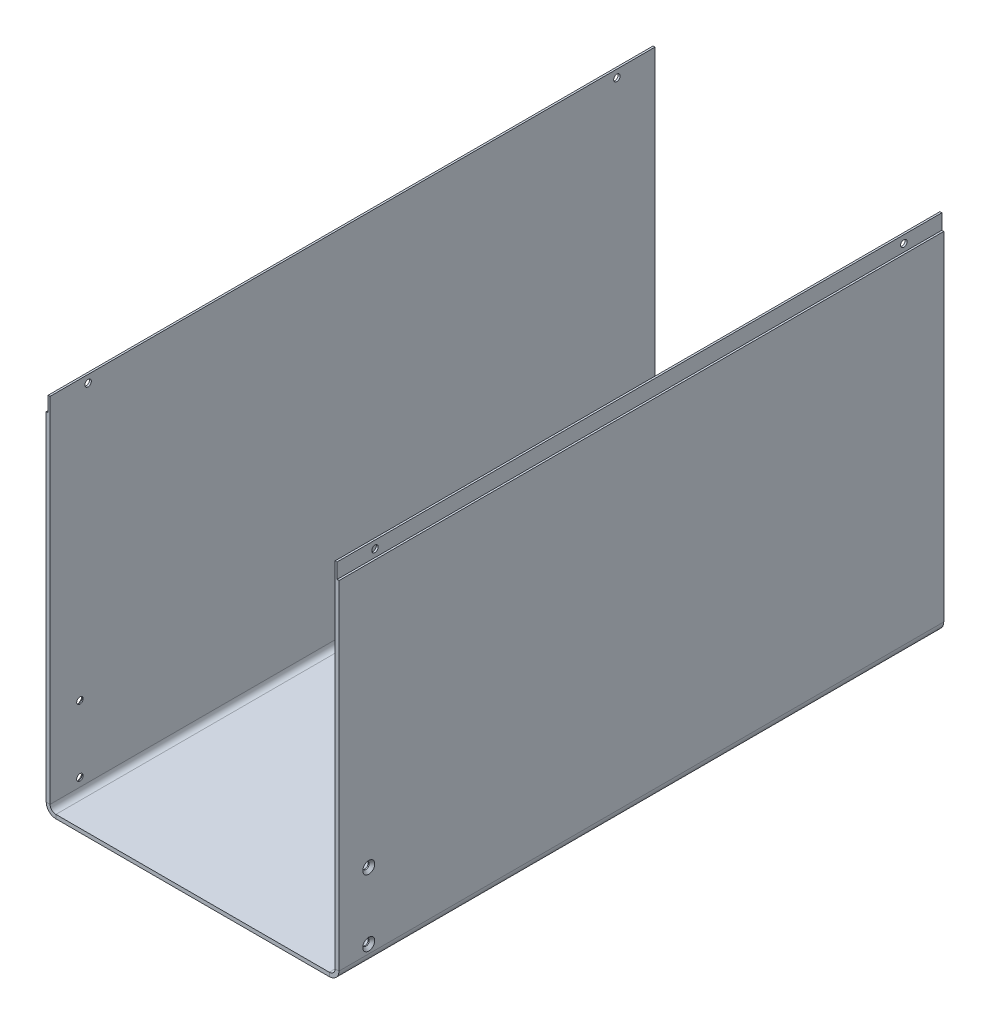
SolidWorks part; units mm, degrees
note: The reader was unsure of these and kept them because the rebuilt part matched: flange length of "Edge-Flange1"; thickness of "Edge-Flange1".
ref_plane "Front Plane" through (0, 0, 0) normal (0, 0, 1) x (1, 0, 0)
ref_plane "Top Plane" through (0, 0, 0) normal (0, 1, 0) x (1, 0, 0)
ref_plane "Right Plane" through (0, 0, 0) normal (1, 0, 0) x (0, 0, -1)
sketch "Sketch1" plane through (0, 0, 0) normal (0, 1, 0) x (1, 0, 0)
  line L1 (0, 0) -> (150, 0)
  line L2 (0, 0) -> (0, 318.3528)
  line L3 (0, 318.3528) -> (150, 318.3528)
  line L4 (150, 0) -> (150, 318.3528)
  line L7 (146.952, 318.3528) -> (3.048, 318.3528) construction
  line L8 (75, 318.3528) -> (75, 354.3857) construction
  line L9 (292.8203, 354.3857) -> (127.8203, 354.3857) construction
  dimension "D1" = 150
base flange "Base-Flange1" sketch "Sketch1" thickness 2.032 reverse thickness direction no parameters "D1"=3.048
edge flange "Edge-Flange1" sketch "Sketch6" flange profiles "Sketch6", "Sketch8" flange angle 90 flange length 189.048 flange position material outside bend radius 3.048 thickness 2.032 relief rectangular parameters "D6"=10, "D8"=1
sketch "Sketch6" plane through (150, 0, 0) normal (1, 0, 0) x (0, 0, -1)
  line L2 (0, 0) -> (0, 189.048)
  line L3 (0, 189.048) -> (318.3528, 189.048)
  line L4 (318.3528, 189.048) -> (318.3528, 0)
  line L7 (0, 0) -> (318.3528, 0) construction
  line L8 (0, 0) -> (318.3528, 0)
sketch "Sketch8" plane through (0, 0, 0) normal (-1, 0, 0) x (0, 0, 1)
  line L0 (-318.3528, 0) -> (0, 0) construction
  line L1 (-318.3528, 0) -> (0, 0)
  line L2 (-318.3528, 0) -> (-318.3528, 189.048)
  line L3 (-318.3528, 189.048) -> (0, 189.048)
  line L4 (0, 189.048) -> (0, 0)
bend "EdgeBend1" bend radius 3.048 bend angle 90 parameters "D5"=1
bend "EdgeBend2" bend radius 3.048 bend angle 90 parameters "D5"=3
sketch "Sketch9" plane through (152.032, 0, 0) normal (1, 0, 0) x (0, 0, -1)
  line L0 (318.3528, 3.048) -> (318.3528, 189.048) construction
  line L1 (0, 189.048) -> (318.3528, 189.048)
  line L2 (0, 189.048) -> (0, 181.048)
  line L3 (0, 181.048) -> (318.3528, 181.048)
  line L4 (318.3528, 189.048) -> (318.3528, 181.048)
  dimension "D1" = 8
extrude "Cut-Extrude1" cut sketch "Sketch9" against normal blind 1.016 normal cut yes
sketch "Sketch10" plane through (-2.032, 0, -3.175) normal (1, 0, 0) x (0, 0, -1)
  line L1 (-3.175, 189.048) -> (315.1778, 189.048)
  line L2 (-3.175, 189.048) -> (-3.175, 181.048)
  line L3 (-3.175, 181.048) -> (315.1778, 181.048)
  line L4 (315.1778, 189.048) -> (315.1778, 181.048)
  line L5 (-3.175, 3.048) -> (-3.175, 189.048) construction
  dimension "D1" = 8
extrude "Cut-Extrude3" cut sketch "Sketch10" along normal blind 1.016 normal cut yes
sketch "Sketch11" plane through (151.016, 0, 0) normal (1, 0, 0) x (0, 0, -1)
  line L0 (0, 185.048) -> (20.0033, 185.048) construction
  line L1 (0, 189.048) -> (0, 181.048) construction
  line L2 (318.3528, 185.048) -> (298.3528, 185.048) construction
  line L3 (318.3528, 181.048) -> (318.3528, 189.048) construction
  dimension "D1" = 20.0033
  dimension "D2" = 20
hole_wizard "M3 Clearance Hole1" positions "Sketch12" profile "Sketch13" hole size "M3" standard "ANSI Metric" end condition through all
sketch "Sketch12" plane through (151.016, 0, 0) normal (1, 0, 0) x (0, 0, -1)
  point P0 (20.0033, 185.048)
  point P3 (298.3528, 185.048)
sketch "Sketch13" plane through (151.016, 185.048, -20.0033) normal (0, 1, 0) x (0, 0, -1)
  line L0 (0, 0) -> (0, 153.048)
  line L1 (0, 153.048) -> (1.7, 153.048)
  line L2 (1.7, 153.048) -> (1.7, 0)
  line L5 (1.7, 0) -> (0, 0)
  line L11 (0, -6.35) -> (0, 107.95) construction
  dimension "Thru Hole Dia." = 3.4
  dimension "Thru Hole Depth" = 153.048
sketch "Sketch16" plane through (152.032, 0, 0) normal (1, 0, 0) x (0, 0, -1)
  line L0 (5.5, 181.048) -> (5.5, 175.048) construction
  line L1 (0, 181.048) -> (318.3528, 181.048) construction
  line L2 (5.5, 175.048) -> (0, 175.048) construction
  line L3 (0, 181.048) -> (0, 3.048) construction
  dimension "D1" = 6
  dimension "D2" = 5.5
hole_wizard "CSK for M3 Flat Head Machine Screw1" positions "Sketch19" profile "Sketch20" countersink size "M3" standard "ANSI Metric" end condition up to next
sketch "Sketch19" plane through (152.032, 0, 0) normal (1, 0, 0) x (0, 0, -1)
  point P0 (15.7004, 42.5)
  point P6 (15.7004, 7.5)
sketch "Sketch20" plane through (152.032, 42.5, -15.7004) normal (0, 1, 0) x (0, 0, -1)
  line L0 (0, 0) -> (0, 2.032)
  line L1 (0, 2.032) -> (1.7, 2.032)
  line L2 (1.7, 2.032) -> (1.7, 1.45)
  line L3 (1.7, 1.45) -> (3.15, 0)
  line L5 (3.15, 0) -> (0, 0)
  line L6 (-1.7, 1.45) -> (-3.15, 0) construction
  line L11 (0, -6.35) -> (0, 107.95) construction
  dimension "Thru Hole Dia." = 3.4
  dimension "Thru Hole Depth" = 2.032
  dimension "Near C'Sink Dia." = 6.3
  dimension "Near C'Sink Angle" = 90
hole_wizard "CSK for M3 Flat Head Machine Screw2" positions "Sketch22" profile "Sketch23" countersink size "M3" standard "ANSI Metric" end condition up to next
sketch "Sketch22" plane through (-2.032, 0, 0) normal (-1, 0, 0) x (0, 0, 1)
  point P0 (-15.7004, 42.5)
  point P3 (-15.7004, 7.5)
sketch "Sketch23" plane through (-2.032, 42.5, -15.7004) normal (0, 1, 0) x (0, 0, 1)
  line L0 (0, 0) -> (0, 2.032)
  line L1 (0, 2.032) -> (1.7, 2.032)
  line L2 (1.7, 2.032) -> (1.7, 1.45)
  line L3 (1.7, 1.45) -> (3.15, 0)
  line L5 (3.15, 0) -> (0, 0)
  line L6 (-1.7, 1.45) -> (-3.15, 0) construction
  line L11 (0, -6.35) -> (0, 107.95) construction
  dimension "Thru Hole Dia." = 3.4
  dimension "Thru Hole Depth" = 2.032
  dimension "Near C'Sink Dia." = 6.3
  dimension "Near C'Sink Angle" = 90
sketch "Bend-Lines1" [suppressed] plane through (0, 0, 0) normal (0, 1, 0) x (1, 0, 0)
sketch "Bounding-Box1" [suppressed] plane through (0, 0, 0) normal (0, 1, 0) x (1, 0, 0)
sheet metal parameters "Sheet-Metal1" thickness 2.032 parameters "D1"=1.016
flat pattern "Flat-Pattern1" [suppressed]
sketch "Bend-Lines2" plane through (0, 0, 0) normal (0, 1, 0) x (1, 0, 0)
sketch3d "Bounding-Box2" [suppressed]
  line L0 (0, 0, 0) -> (0, 326.228, 0) construction
  line L1 (150, 0, 0) -> (150, 326.228, 0) construction
  line L2 (0, 0, 0) -> (150, 0, 0) construction
  line L3 (0, 326.228, 0) -> (150, 326.228, 0) construction
sheet metal parameters "Sheet-Metal2" thickness 2.032 parameters "D1"=1.016, "D7"=3.175
flat pattern "Flat-Pattern1"
sketch "Bend-Lines2" plane through (0, 0, 0) normal (0, 1, 0) x (1, 0, 0)
  line L0 (150.2248, 0) -> (150.2248, 326.228) construction
  line L1 (150.2248, 0) -> (150.2248, 326.228) construction
  line L2 (-0.2248, 326.228) -> (-0.2248, 0) construction
  line L3 (-0.2248, 326.228) -> (-0.2248, 0) construction
sketch3d "Bounding-Box2" [suppressed]
  line L0 (-15.4976, 0, 0) -> (-15.4976, 326.228, 0) construction
  line L1 (165.4976, 0, 0) -> (165.4976, 326.228, 0) construction
  line L2 (-15.4976, 0, 0) -> (165.4976, 0, 0) construction
  line L3 (-15.4976, 326.228, 0) -> (165.4976, 326.228, 0) construction
bend of the flat pattern "Flatten-<EdgeBend1>1"
bend of the flat pattern "Flatten-<EdgeBend2>1"
sheet metal parameters "Sheet-Metal3" thickness 2.032 parameters "D1"=1.016, "D7"=3.175
flat pattern "Flat-Pattern1"
sketch "Bend-Lines2" plane through (0, 0, 0) normal (0, 1, 0) x (1, 0, 0)
  line L0 (150.2248, 0) -> (150.2248, 326.228) construction
  line L1 (150.2248, 0) -> (150.2248, 326.228) construction
  line L2 (-0.2248, 326.228) -> (-0.2248, 0) construction
  line L3 (-0.2248, 326.228) -> (-0.2248, 0) construction
sketch3d "Bounding-Box2" [suppressed]
  line L0 (-15.4976, 0, 0) -> (-15.4976, 326.228, 0) construction
  line L1 (165.4976, 0, 0) -> (165.4976, 326.228, 0) construction
  line L2 (-15.4976, 0, 0) -> (165.4976, 0, 0) construction
  line L3 (-15.4976, 326.228, 0) -> (165.4976, 326.228, 0) construction
bend of the flat pattern "Flatten-<EdgeBend1>1"
bend of the flat pattern "Flatten-<EdgeBend2>1"
sheet metal parameters "Sheet-Metal4" thickness 2.032 parameters "D1"=1.016, "D7"=3.175
flat pattern "Flat-Pattern1"
sketch "Bend-Lines2" plane through (0, 0, 0) normal (0, 1, 0) x (1, 0, 0)
  line L0 (150.2248, 0) -> (150.2248, 326.228) construction
  line L1 (150.2248, 0) -> (150.2248, 326.228) construction
  line L2 (-0.2248, 326.228) -> (-0.2248, 0) construction
  line L3 (-0.2248, 326.228) -> (-0.2248, 0) construction
sketch3d "Bounding-Box2" [suppressed]
  line L0 (350.4976, 326.228, 0) -> (-200.4976, 326.228, 0) construction
  line L1 (350.4976, 0, 0) -> (-200.4976, 0, 0) construction
  line L2 (350.4976, 326.228, 0) -> (350.4976, 0, 0) construction
  line L3 (-200.4976, 326.228, 0) -> (-200.4976, 0, 0) construction
bend of the flat pattern "Flatten-<EdgeBend1>1"
bend of the flat pattern "Flatten-<EdgeBend2>1"
sheet metal parameters "Sheet-Metal5" thickness 2.032 parameters "D1"=1.016, "D7"=3.175
flat pattern "Flat-Pattern1" [suppressed]
sketch "Bend-Lines2" plane through (0, 0, 0) normal (0, 1, 0) x (1, 0, 0)
  line L0 (150.1439, 0) -> (150.1439, 318.048) construction
  line L1 (150.1439, 0) -> (150.1439, 318.048) construction
  line L2 (-0.1439, 318.048) -> (-0.1439, 0) construction
  line L3 (-0.1439, 318.048) -> (-0.1439, 0) construction
sketch3d "Bounding-Box2" [suppressed]
  line L0 (339.3357, 318.048, 0) -> (-189.3357, 318.048, 0) construction
  line L1 (339.3357, 0, 0) -> (-189.3357, 0, 0) construction
  line L2 (339.3357, 318.048, 0) -> (339.3357, 0, 0) construction
  line L3 (-189.3357, 318.048, 0) -> (-189.3357, 0, 0) construction
bend of the flat pattern "Flatten-<EdgeBend1>1"
bend of the flat pattern "Flatten-<EdgeBend2>1"
sketch "Sketch16-1" plane through (150.2877, -2.032, 0) normal (0, -1, 0) x (0, 0, -1)
  line L0 (5.5, 181.048) -> (5.5, 175.048) construction
  line L2 (5.5, 175.048) -> (0, 175.048) construction
  dimension "D1" = 6
  dimension "D2" = 5.5
sheet metal parameters "Sheet-Metal7" thickness 2.032 parameters "D1"=1.016, "D7"=3.175
flat pattern "Flat-Pattern1" [suppressed]
sketch "Bend-Lines2" plane through (0, 0, 0) normal (0, 1, 0) x (1, 0, 0)
  line L0 (150.1439, 0) -> (150.1439, 318.048) construction
  line L1 (150.1439, 0) -> (150.1439, 318.048) construction
  line L2 (-0.1439, 318.048) -> (-0.1439, 0) construction
  line L3 (-0.1439, 318.048) -> (-0.1439, 0) construction
sketch3d "Bounding-Box2" [suppressed]
  line L0 (339.3357, 318.048, 0) -> (-189.3357, 318.048, 0) construction
  line L1 (339.3357, 0, 0) -> (-189.3357, 0, 0) construction
  line L2 (339.3357, 318.048, 0) -> (339.3357, 0, 0) construction
  line L3 (-189.3357, 318.048, 0) -> (-189.3357, 0, 0) construction
bend of the flat pattern "Flatten-<EdgeBend1>1"
bend of the flat pattern "Flatten-<EdgeBend2>1"
sketch "Sketch16-2" plane through (150.2877, -2.032, 0) normal (0, -1, 0) x (0, 0, -1)
  line L0 (5.5, 181.048) -> (5.5, 175.048) construction
  line L2 (5.5, 175.048) -> (0, 175.048) construction
  dimension "D1" = 6
  dimension "D2" = 5.5
sheet metal parameters "Sheet-Metal8" thickness 2.032 parameters "D1"=1.016, "D7"=3.175
flat pattern "Flat-Pattern1" [suppressed]
sketch "Bend-Lines2" plane through (0, 0, 0) normal (0, 1, 0) x (1, 0, 0)
  line L0 (150.1439, 0) -> (150.1439, 318.3528) construction
  line L1 (150.1439, 0) -> (150.1439, 318.3528) construction
  line L2 (-0.1439, 318.3528) -> (-0.1439, 0) construction
  line L3 (-0.1439, 318.3528) -> (-0.1439, 0) construction
sketch3d "Bounding-Box2" [suppressed]
  line L0 (339.3357, 318.3528, 0) -> (-189.3357, 318.3528, 0) construction
  line L1 (339.3357, 0, 0) -> (-189.3357, 0, 0) construction
  line L2 (339.3357, 318.3528, 0) -> (339.3357, 0, 0) construction
  line L3 (-189.3357, 318.3528, 0) -> (-189.3357, 0, 0) construction
bend of the flat pattern "Flatten-<EdgeBend1>1"
bend of the flat pattern "Flatten-<EdgeBend2>1"
sketch "Sketch16-2" plane through (150.2877, -2.032, 0) normal (0, -1, 0) x (0, 0, -1)
  line L0 (5.5, 181.048) -> (5.5, 175.048) construction
  line L2 (5.5, 175.048) -> (0, 175.048) construction
  dimension "D1" = 6
  dimension "D2" = 5.5
equation "\"D1@Cut-Extrude1\"=\"Thickness\"/2"
equation "\"D1@Cut-Extrude3\"=\"Thickness\"/2"
